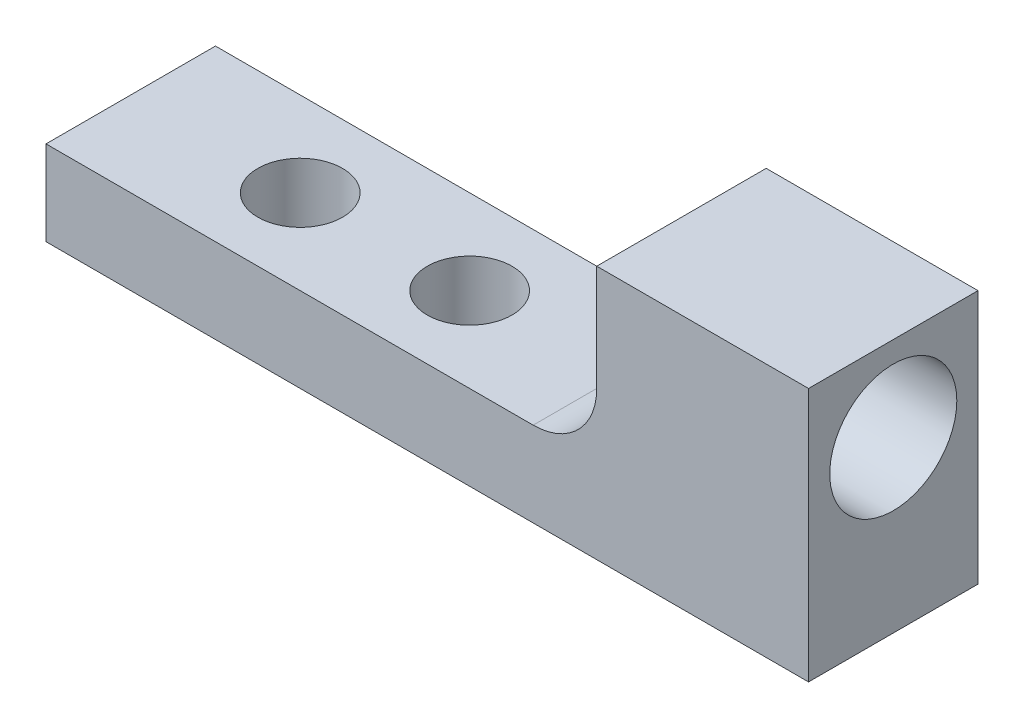
SolidWorks part; units mm, degrees
material "AISI 304"
ref_plane "Front" through (0, 0, 0) normal (0, 0, 1) x (1, 0, 0)
ref_plane "Top" through (0, 0, 0) normal (0, 1, 0) x (1, 0, 0)
ref_plane "Right" through (0, 0, 0) normal (1, 0, 0) x (0, 0, -1)
sketch "Sketch1" plane through (0, 0, 0) normal (0, 1, 0) x (1, 0, 0)
  line L1 (-14.2875, -3.175) -> (14.2875, -3.175)
  line L2 (-14.2875, -3.175) -> (-14.2875, 3.175)
  line L3 (-14.2875, 3.175) -> (14.2875, 3.175)
  line L4 (14.2875, -3.175) -> (14.2875, 3.175)
  line L5 (-14.2875, -3.175) -> (14.2875, 3.175) construction
  line L6 (-14.2875, 3.175) -> (14.2875, -3.175) construction
  line L7 (14.2875, 3.175) -> (6.35, 3.175)
  line L8 (14.2875, 3.175) -> (14.2875, -3.175)
  line L9 (14.2875, -3.175) -> (6.35, -3.175)
  line L10 (6.35, 3.175) -> (6.35, -3.175)
  circle A0 centre (-7.9375, 0) radius 1.5875
  circle A1 centre (-1.5875, 0) radius 1.5875
  point P0 (0, 0)
  point P10 (0, 0)
  dimension "D4" = 3.175
  dimension "D1" = 28.575
  dimension "D2" = 6.35
  dimension "D3" = 6.35
  dimension "D5" = 6.35
  dimension "D6" = 20.6375
extrude "Boss-Extrude1" add sketch "Sketch1" along normal blind 3.175 contours L10 L3 L2 L1 A1 A0 region at (-3.8597, 0, 0)
extrude "Boss-Extrude2" add sketch "Sketch1<3>" along normal blind 9.525 contours L3 L10 L1 L4 region at (10.3187, 0, 0)
sketch "Sketch1<3>" plane through (0, 0, 0) normal (0, 1, 0) x (1, 0, 0) same geometry as "Sketch1"
fillet "Fillet1" radius 2.3813 1 edges at (6.35, 3.175, 0)
sketch "Sketch2" plane through (14.2875, 0, 0) normal (1, 0, 0) x (0, 0, -1)
  line L0 (3.175, 9.525) -> (-3.175, 9.525) construction
  line L1 (-3.175, 3.175) -> (3.175, 3.175) construction
  line L2 (3.175, 9.525) -> (-3.175, 9.525)
  line L3 (-3.175, 3.175) -> (3.175, 3.175)
  line L4 (0, 3.175) -> (0, 9.525) construction
  circle A0 centre (0, 6.35) radius 2.3812
  point P9 (0, 6.35)
  dimension "D1" = 4.7625
extrude "Cut-Extrude1" cut sketch "Sketch2" against normal through all contours A0 L4 | L4 A0 region at (14.2875, 6.35, 1.0106) region at (14.2875, 6.35, -1.0106)
